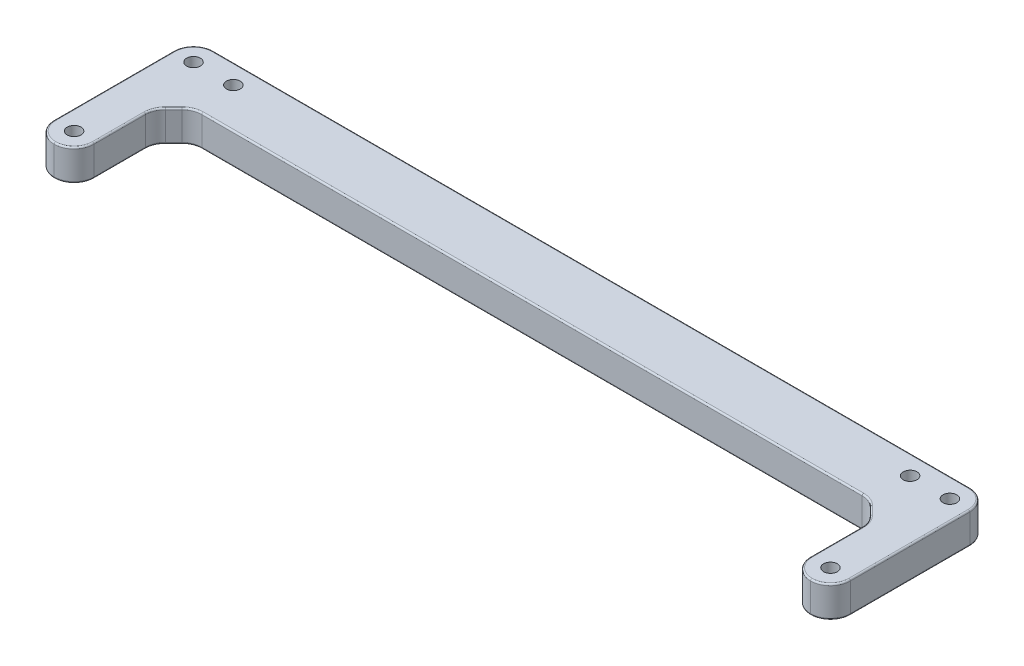
SolidWorks part; units mm, degrees
ref_plane "Front Plane" through (0, 0, 0) normal (0, 0, 1) x (1, 0, 0)
ref_plane "Top Plane" through (0, 0, 0) normal (0, 1, 0) x (1, 0, 0)
ref_plane "Right Plane" through (0, 0, 0) normal (1, 0, 0) x (0, 0, -1)
sketch "Sketch1" plane through (0, 0, 0) normal (0, 1, 0) x (1, 0, 0)
  line L0 (127, 0) -> (-127, 0)
  line L1 (0, 0) -> (0, -19.05) construction
  line L2 (-120.65, -6.35) -> (-107.95, -6.35) construction
  line L3 (-127, 0) -> (-127, -50.8)
  line L4 (-127, -50.8) -> (-114.3, -50.8)
  line L5 (-114.3, -50.8) -> (-114.3, -25.4)
  line L6 (-114.3, -25.4) -> (-107.95, -19.05)
  line L7 (-107.95, -19.05) -> (107.95, -19.05)
  line L8 (-120.65, -6.35) -> (-120.65, -44.45) construction
  line L9 (127, 0) -> (127, -50.8)
  line L10 (127, -50.8) -> (114.3, -50.8)
  line L11 (114.3, -50.8) -> (114.3, -25.4)
  line L12 (114.3, -25.4) -> (107.95, -19.05)
  circle A0 centre (-120.65, -6.35) radius 2.2
  circle A3 centre (-107.95, -6.35) radius 2.2
  circle A4 centre (-120.65, -44.45) radius 2.2
  circle A5 centre (120.65, -44.45) radius 2.2
  circle A6 centre (107.95, -6.35) radius 2.2
  circle A7 centre (120.65, -6.35) radius 2.2
  point P4 (0, 0)
  dimension "D9" = 4.4
  dimension "D1" = 12.7
  dimension "D2" = 127
  dimension "D3" = 50.8
  dimension "D4" = 45
  dimension "D5" = 19.05
  dimension "D6" = 25.4
  dimension "D7" = 6.35
  dimension "D8" = 6.35
  dimension "D11" = 12.7
  dimension "D13" = 38.1
  dimension "D10" = 2
  dimension "D12" = 2
extrude "Boss-Extrude1" add sketch "Sketch1" along normal blind 10
fillet "Fillet1" radius 6.35 6 edges at (127, 5, 0) (127, 5, 50.8) (114.3, 5, 50.8) (-114.3, 5, 50.8) (-127, 5, 50.8) (-127, 5, 0)
fillet "Fillet2" radius 6.35 4 edges at (114.3, 5, 25.4) (107.95, 5, 19.05) (-114.3, 5, 25.4) (-107.95, 5, 19.05)
fillet "Fillet3" radius 0.5 36 edges at (-125.1401, 0, 1.8599) (0, 0, 0) (125.1401, 0, 1.8599) (127, 0, 25.4) (125.1401, 0, 48.9401) (116.1599, 0, 48.9401) (114.3, 0, 36.2401) (113.8166, 0, 25.6002) (111.125, 0, 22.225) (107.7498, 0, 19.5334) (0, 0, 19.05) (-107.7498, 0, 19.5334) (-111.125, 0, 22.225) (-113.8166, 0, 25.6002) (-114.3, 0, 36.2401) (-116.1599, 0, 48.9401) (-125.1401, 0, 48.9401) (-125.1401, 10, 1.8599) (0, 10, 0) (125.1401, 10, 1.8599) (127, 10, 25.4) (125.1401, 10, 48.9401) (116.1599, 10, 48.9401) (114.3, 10, 36.2401) (113.8166, 10, 25.6002) (111.125, 10, 22.225) (107.7498, 10, 19.5334) (0, 10, 19.05) (-107.7498, 10, 19.5334) (-111.125, 10, 22.225) (-113.8166, 10, 25.6002) (-114.3, 10, 36.2401) (-116.1599, 10, 48.9401) (-125.1401, 10, 48.9401) (-127, 0, 25.4) (-127, 10, 25.4)
